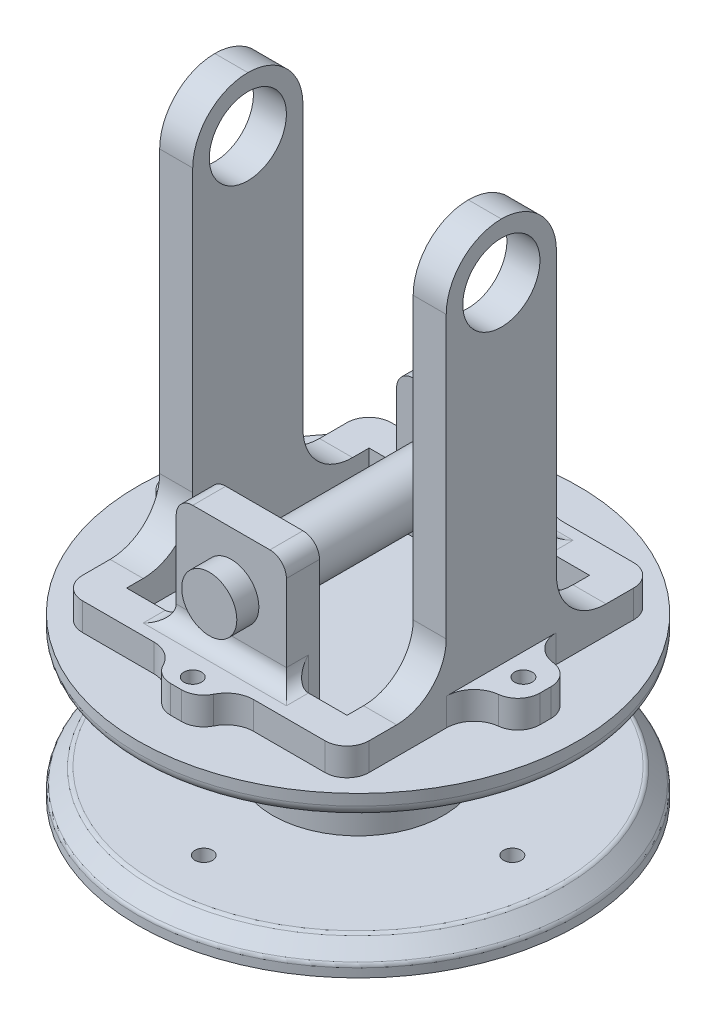
SolidWorks part; units mm, degrees
ref_plane "Alzado" through (0, 0, 0) normal (0, 0, 1) x (1, 0, 0)
ref_plane "Planta" through (0, 0, 0) normal (0, 1, 0) x (1, 0, 0)
ref_plane "Vista lateral" through (0, 0, 0) normal (1, 0, 0) x (0, 0, -1)
sketch "Croquis1" plane through (0, 0, 0) normal (0, 1, 0) x (1, 0, 0)
  circle A0 centre (0, 0) radius 40
  circle A1 centre (0, 28) radius 1.6
  circle A2 centre (28, 0) radius 1.6
  circle A3 centre (0, -28) radius 1.6
  circle A4 centre (-28, 0) radius 1.6
  dimension "D1" = 80
  dimension "D2" = 3.2
  dimension "D3" = 28
  dimension "D4" = 4
extrude "Saliente-Extruir1" add sketch "Croquis1" along normal blind 5
chamfer "Chaflán1" distance 3 angle 45 1 edges at (0, 5, 40)
fillet "Redondeo1" radius 1 2 edges at (0, 5, 37) (0, 2, 40)
sketch "Croquis4" plane through (0, 5, 0) normal (0, 1, 0) x (1, 0, 0)
  line L1 (0, 7.5056) -> (-6.5, 3.7528)
  line L2 (-6.5, 3.7528) -> (-6.5, -3.7528)
  line L3 (-6.5, -3.7528) -> (0, -7.5056)
  line L4 (0, -7.5056) -> (6.5, -3.7528)
  line L5 (6.5, -3.7528) -> (6.5, 3.7528)
  line L6 (6.5, 3.7528) -> (0, 7.5056)
  circle A0 centre (0, 0) radius 6.5 construction
  dimension "D1" = 13
extrude "Cortar-Extruir1" cut sketch "Croquis4" against normal blind 5
sketch "Croquis5" plane through (0, 5, 0) normal (0, 1, 0) x (1, 0, 0)
  line L0 (0, 7.5056) -> (-6.5, 3.7528) construction
  line L1 (-6.5, 3.7528) -> (-6.5, -3.7528) construction
  line L2 (-6.5, -3.7528) -> (0, -7.5056) construction
  line L3 (0, -7.5056) -> (6.5, -3.7528) construction
  line L4 (6.5, -3.7528) -> (6.5, 3.7528) construction
  line L5 (6.5, 3.7528) -> (0, 7.5056) construction
  line L6 (0, 7.5056) -> (-6.5, 3.7528)
  line L7 (-6.5, 3.7528) -> (-6.5, -3.7528)
  line L8 (-6.5, -3.7528) -> (0, -7.5056)
  line L9 (0, -7.5056) -> (6.5, -3.7528)
  line L10 (6.5, -3.7528) -> (6.5, 3.7528)
  line L11 (6.5, 3.7528) -> (0, 7.5056)
  line L12 (0, 10.9697) -> (-9.5, 5.4848)
  line L13 (-9.5, 5.4848) -> (-9.5, -5.4848)
  line L14 (-9.5, -5.4848) -> (0, -10.9697)
  line L15 (0, -10.9697) -> (9.5, -5.4848)
  line L16 (9.5, -5.4848) -> (9.5, 5.4848)
  line L17 (9.5, 5.4848) -> (0, 10.9697)
  dimension "D1" = 3
extrude "Saliente-Extruir3" add sketch "Croquis5" along normal blind 8 contours L12 L13 L14 L15 L16 L17 | L6 L7 L8 L9 L10 L11
sketch "Croquis6" plane through (0, 13, 0) normal (0, 1, 0) x (1, 0, 0)
  line L6 (0, 7.5056) -> (-6.5, 3.7528)
  line L7 (6.5, 3.7528) -> (0, 7.5056)
  line L8 (6.5, -3.7528) -> (6.5, 3.7528)
  line L9 (0, -7.5056) -> (6.5, -3.7528)
  line L10 (-6.5, -3.7528) -> (0, -7.5056)
  line L11 (-6.5, 3.7528) -> (-6.5, -3.7528)
  line L12 (0, 7.5056) -> (-6.5, 3.7528)
  line L13 (6.5, 3.7528) -> (0, 7.5056)
  line L14 (6.5, -3.7528) -> (6.5, 3.7528)
  line L15 (0, -7.5056) -> (6.5, -3.7528)
  line L16 (-6.5, -3.7528) -> (0, -7.5056)
  line L17 (-6.5, 3.7528) -> (-6.5, -3.7528)
  circle A0 centre (0, 0) radius 4.1
  dimension "D1" = 8.2
  dimension "D2" = 0
extrude "Saliente-Extruir4" add sketch "Croquis6" against normal blind 5
sketch "Croquis7" plane through (0, 5, 0) normal (0, 1, 0) x (1, 0, 0)
  line L6 (9.5, 5.4848) -> (0, 10.9697)
  line L7 (0, 10.9697) -> (-9.5, 5.4848)
  line L8 (-9.5, 5.4848) -> (-9.5, -5.4848)
  line L9 (-9.5, -5.4848) -> (0, -10.9697)
  line L10 (0, -10.9697) -> (9.5, -5.4848)
  line L11 (9.5, -5.4848) -> (9.5, 5.4848)
  line L12 (9.5, 5.4848) -> (0, 10.9697)
  line L13 (0, 10.9697) -> (-9.5, 5.4848)
  line L14 (-9.5, 5.4848) -> (-9.5, -5.4848)
  line L15 (-9.5, -5.4848) -> (0, -10.9697)
  line L16 (0, -10.9697) -> (9.5, -5.4848)
  line L17 (9.5, -5.4848) -> (9.5, 5.4848)
  circle A0 centre (0, 0) radius 12.5
  dimension "D2" = 25
  dimension "D1" = 0
extrude "Saliente-Extruir5" add sketch "Croquis7" along normal up to vertex (8 mm away) up to point (-9.5, 13, 5.4848)
sketch "Croquis9" plane through (0, 5, 0) normal (0, 1, 0) x (1, 0, 0)
  circle A0 centre (0, 0) radius 12.5 construction
  circle A1 centre (0, 0) radius 12.5
  circle A2 centre (0, 0) radius 15.5
  dimension "D1" = 3
extrude "Saliente-Extruir7" add sketch "Croquis9" along normal blind 20 separate body
sketch "Croquis10" plane through (0, 25, 0) normal (0, 1, 0) x (1, 0, 0)
  circle A0 centre (0, 0) radius 12.5 construction
  circle A1 centre (0, 0) radius 12.5
  circle A2 centre (0, 0) radius 8.1
  dimension "D1" = 16.2
extrude "Saliente-Extruir8" add sketch "Croquis10" against normal up to surface (12 mm away) contours A2 | A1 up to face at (0, 13, 4.1)
sketch "Croquis11" plane through (0, 25, 0) normal (0, 1, 0) x (1, 0, 0)
  circle A1 centre (0, 0) radius 40
  dimension "D1" = 80
extrude "Saliente-Extruir9" add sketch "Croquis11" along normal blind 4
fillet "Redondeo2" radius 10 1 edges at (0, 25, 15.5)
sketch "Croquis12" plane through (0, 29, 0) normal (0, 1, 0) x (1, 0, 0)
  line L1 (0, 7.5056) -> (-6.5, 3.7528)
  line L2 (-6.5, 3.7528) -> (-6.5, -3.7528)
  line L3 (-6.5, -3.7528) -> (0, -7.5056)
  line L4 (0, -7.5056) -> (6.5, -3.7528)
  line L5 (6.5, -3.7528) -> (6.5, 3.7528)
  line L6 (6.5, 3.7528) -> (0, 7.5056)
  circle A0 centre (0, 0) radius 6.5 construction
extrude "Cortar-Extruir2" cut sketch "Croquis12" against normal blind 10
sketch "Croquis13" plane through (0, 29, 0) normal (0, 1, 0) x (1, 0, 0)
  line L0 (-6.5, 3.7528) -> (-6.5, -3.7528) construction
  line L1 (-6.5, -3.7528) -> (0, -7.5056) construction
  line L2 (0, -7.5056) -> (6.5, -3.7528) construction
  line L3 (6.5, -3.7528) -> (6.5, 3.7528) construction
  line L4 (0, 7.5056) -> (-6.5, 3.7528) construction
  line L5 (6.5, 3.7528) -> (0, 7.5056) construction
  line L6 (-6.5, 3.7528) -> (-6.5, -3.7528)
  line L7 (-6.5, -3.7528) -> (0, -7.5056)
  line L8 (0, -7.5056) -> (6.5, -3.7528)
  line L9 (6.5, -3.7528) -> (6.5, 3.7528)
  line L10 (0, 7.5056) -> (-6.5, 3.7528)
  line L11 (6.5, 3.7528) -> (0, 7.5056)
extrude "Saliente-Extruir10" add sketch "Croquis13" against normal blind 2
fillet "Redondeo3" radius 2 1 edges at (0, 25, 40)
sketch "Croquis14" plane through (0, 29, 0) normal (0, 1, 0) x (1, 0, 0)
  circle A0 centre (0, 30) radius 1.6
  circle A2 centre (30, 0) radius 1.6
  circle A4 centre (0, -30) radius 1.6
  circle A6 centre (-30, 0) radius 1.6
  circle A8 centre (-21.2132, 21.2132) radius 1.6 [skipped]
  circle A9 centre (21.2132, 21.2132) radius 1.6 [skipped]
  circle A10 centre (-21.2132, -21.2132) radius 1.6 [skipped]
  circle A11 centre (21.2132, -21.2132) radius 1.6 [skipped]
  dimension "D2" = 3.2
  dimension "D1" = 30
  dimension "D3" = 8
extrude "Cortar-Extruir3" cut sketch "Croquis14" against normal up to surface (4 mm away) up to face at (0, 25, 38)
sketch "Croquis15" plane through (0, 29, 0) normal (0, 1, 0) x (1, 0, 0)
  line L0 (20, -22) -> (20, 22)
  line L1 (26, -28) -> (5, -28)
  line L2 (26, -28) -> (26, -5)
  line L3 (26, 28) -> (5, 28)
  line L4 (-26, -28) -> (-26, -5)
  line L5 (26, -28) -> (-26, 28) construction
  line L6 (26, 28) -> (-26, -28) construction
  line L7 (20, 22) -> (-20, 22)
  line L8 (-20, -22) -> (-20, 22)
  line L9 (20, -22) -> (-20, -22)
  line L10 (-26, 5) -> (-26, 28)
  line L11 (-34, 5) -> (-26, 5)
  line L12 (-34, 5) -> (-34, -5)
  line L13 (-34, -5) -> (-26, -5)
  line L15 (26, 5) -> (34, 5)
  line L17 (26, -5) -> (34, -5)
  line L18 (34, 5) -> (34, -5)
  line L20 (-5, 28) -> (-5, 33)
  line L21 (-5, 33) -> (5, 33)
  line L22 (5, 28) -> (5, 33)
  line L24 (-5, -28) -> (-5, -33)
  line L25 (-5, -33) -> (5, -33)
  line L26 (5, -28) -> (5, -33)
  line L27 (-26, -28) -> (-26, 28) construction
  line L28 (-5, 28) -> (-26, 28)
  line L29 (26, 28) -> (-26, 28) construction
  line L30 (26, 5) -> (26, 28)
  line L31 (26, -28) -> (26, 28) construction
  line L32 (-5, -28) -> (-26, -28)
  line L33 (26, -28) -> (-26, -28) construction
  circle A0 centre (0, -30) radius 1.6 construction
  circle A1 centre (0, -30) radius 1.6
  circle A2 centre (30, 0) radius 1.6 construction
  circle A3 centre (0, 30) radius 1.6 construction
  circle A4 centre (-30, 0) radius 1.6 construction
  circle A5 centre (30, 0) radius 1.6
  circle A6 centre (0, 30) radius 1.6
  circle A7 centre (-30, 0) radius 1.6
  point P0 (0, 0)
  point P26 (0, 33)
  point P27 (0, -33)
  point P28 (-34, 0)
  point P29 (34, 0)
  dimension "D1" = 56
  dimension "D2" = 52
  dimension "D4" = 10
  dimension "D5" = 5
  dimension "D6" = 5
  dimension "D7" = 8
  dimension "D8" = 10
  dimension "D9" = 8
  dimension "D3" = 6
extrude "Saliente-Extruir11" add sketch "Croquis15" along normal blind 5 separate body
fillet "Redondeo4" radius 4 12 edges at (26, 31.5, 28) (34, 31.5, -5) (26, 31.5, -28) (5, 31.5, -33) (-5, 31.5, -33) (-26, 31.5, -28) (-34, 31.5, -5) (-34, 31.5, 5) (34, 31.5, 5) (5, 31.5, 33) (-5, 31.5, 33) (-26, 31.5, 28)
sketch "Croquis16" plane through (0, 34, 0) normal (0, 1, 0) x (1, 0, 0)
  line L1 (-20, 10) -> (-26, 10)
  line L2 (-20, 10) -> (-20, -10)
  line L3 (-20, -10) -> (-26, -10)
  line L4 (-26, 10) -> (-26, -10)
  line L6 (20, 10) -> (26, 10)
  line L7 (20, 10) -> (20, -10)
  line L8 (20, -10) -> (26, -10)
  line L9 (26, 10) -> (26, -10)
  line L11 (20, -22) -> (20, 22) construction
  line L12 (-20, 22) -> (-20, -22) construction
  line L13 (-26, -5) -> (-26, -24) construction
  line L14 (26, -24) -> (26, -5) construction
  point P14 (-20, 0)
  dimension "D1" = 20
extrude "Saliente-Extruir12" add sketch "Croquis16" along normal blind 70
fillet "Redondeo5" radius 10 4 edges at (23, 104, -10) (23, 104, 10) (-23, 104, -10) (-23, 104, 10)
sketch "Croquis18" plane through (-26, 0, 0) normal (-1, 0, 0) x (0, 0, 1)
  circle A0 centre (0, 94) radius 7
  dimension "D1" = 14
extrude "Cortar-Extruir4" cut sketch "Croquis18" against normal up to surface (52 mm away) up to face at (26, 47.3955, 0)
fillet "Redondeo6" radius 9 4 edges at (23, 34, 10) (23, 34, -10) (-23, 34, -10) (-23, 34, 10)
fillet "Redondeo7" radius 5 8 edges at (5, 31.5, -28) (-5, 31.5, -28) (-26, 31.5, -5) (-26, 31.5, 5) (-5, 31.5, 28) (5, 31.5, 28) (26, 31.5, 5) (26, 31.5, -5)
sketch "Croquis19" plane through (0, 34, 0) normal (0, 1, 0) x (1, 0, 0)
  line L0 (-20, -22) -> (20, -22) construction
  line L1 (-10, -22) -> (10, -22)
  line L2 (-10, -22) -> (-10, -17)
  line L3 (-10, -17) -> (10, -17)
  line L4 (10, -22) -> (10, -17)
  line L5 (20, 22) -> (-20, 22) construction
  line L6 (-10, 22) -> (10, 22)
  line L7 (-10, 22) -> (-10, 17)
  line L8 (-10, 17) -> (10, 17)
  line L9 (10, 22) -> (10, 17)
  point P7 (0, -17)
  dimension "D1" = 5
  dimension "D2" = 20
  dimension "D3" = 5
extrude "Saliente-Extruir13" add sketch "Croquis19" against normal up to surface (5 mm away) up to face at (0, 29, -28.4)
sketch "Croquis20" plane through (0, 34, 0) normal (0, 1, 0) x (1, 0, 0)
  line L0 (10, -22) -> (10, -17) construction
  line L1 (-10, 17) -> (10, 17)
  line L2 (-10, 17) -> (-10, 23)
  line L3 (-10, 23) -> (10, 23)
  line L4 (10, 17) -> (10, 23)
  line L5 (-10, -17) -> (10, -17)
  line L6 (-10, -17) -> (-10, -23)
  line L7 (-10, -23) -> (10, -23)
  line L8 (10, -17) -> (10, -23)
  line L9 (10, 17) -> (10, 22) construction
  dimension "D1" = 6
  dimension "D2" = 6
extrude "Saliente-Extruir14" add sketch "Croquis20" along normal blind 20
sketch "Croquis21" plane through (0, 0, 23) normal (0, 0, 1) x (1, 0, 0)
  line L0 (-10, 54) -> (-10, 34) construction
  circle A0 centre (0, 44) radius 5
  point P5 (-10, 44)
  dimension "D1" = 10
extrude "Cortar-Extruir5" cut sketch "Croquis21" against normal up to surface (46 mm away) up to face at (0, 44, -23)
fillet "Redondeo9" radius 3 10 edges at (10, 31.5, 22) (-10, 31.5, 22) (-10, 31.5, -22) (10, 31.5, -22) (0, 34, -23) (0, 34, 23) (-10, 54, -20) (10, 54, -20) (10, 54, 20) (-10, 54, 20)
fillet "Redondeo10" radius 3 4 edges at (-10, 34, 22.5) (10, 34, 22.5) (-10, 34, -22.5) (10, 34, -22.5)
sketch "Croquis22" plane through (0, 0, 23) normal (0, 0, 1) x (1, 0, 0)
  circle A0 centre (0, 44) radius 5 construction
  circle A1 centre (0, 44) radius 5
extrude "Saliente-Extruir15" add sketch "Croquis22" against normal blind 50 separate body
sketch "Croquis23" plane through (0, 0, 23) normal (0, 0, 1) x (1, 0, 0)
  circle A1 centre (0, 44) radius 5
  circle A2 centre (0, 44) radius 5
  dimension "D1" = 0
extrude "Saliente-Extruir16" add sketch "Croquis23" along normal blind 4
